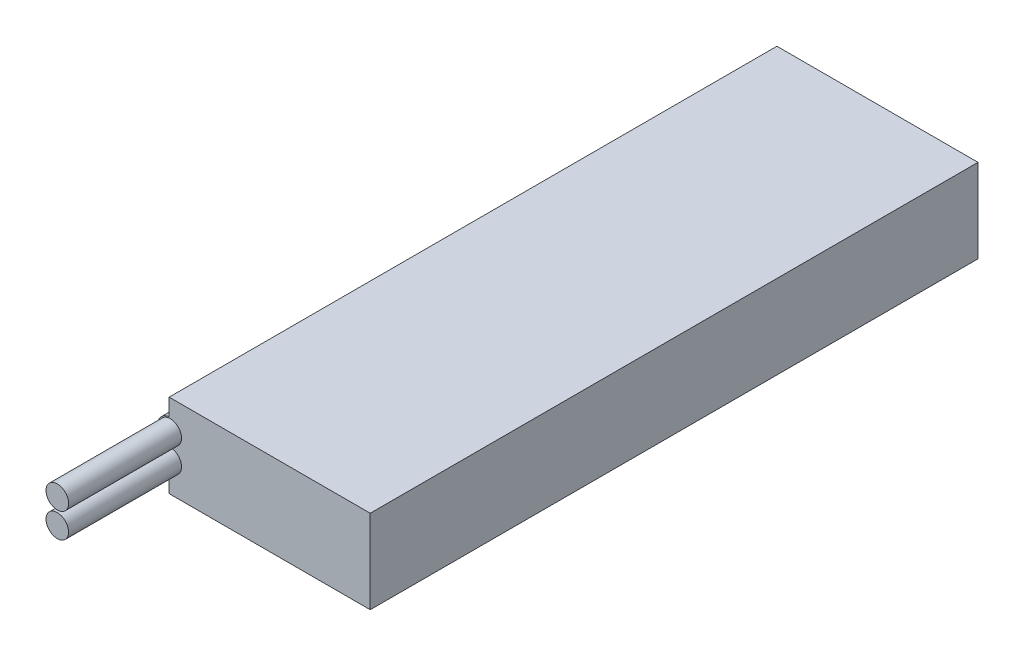
SolidWorks part; units mm, degrees
material "PLA_Battery"
ref_plane "Front Plane" through (0, 0, 0) normal (0, 0, 1) x (1, 0, 0)
ref_plane "Top Plane" through (0, 0, 0) normal (0, 1, 0) x (1, 0, 0)
ref_plane "Right Plane" through (0, 0, 0) normal (1, 0, 0) x (0, 0, -1)
sketch "Sketch1" plane through (0, 0, 0) normal (0, 1, 0) x (1, 0, 0)
  line L1 (-22.25, -67.25) -> (22.25, -67.25)
  line L2 (-22.25, -67.25) -> (-22.25, 67.25)
  line L3 (-22.25, 67.25) -> (22.25, 67.25)
  line L4 (22.25, -67.25) -> (22.25, 67.25)
  line L5 (-22.25, -67.25) -> (22.25, 67.25) construction
  line L6 (-22.25, 67.25) -> (22.25, -67.25) construction
  point P0 (0, 0)
  dimension "D1" = 44.5
  dimension "D2" = 134.5
extrude "Boss-Extrude1" add sketch "Sketch1" along normal blind 18.5
sketch "Imagen" plane through (0, 18.5, 0) normal (0, 1, 0) x (1, 0, 0)
  line L0 (105.6667, 103.5) -> (539.1806, 103.5) construction
  line L1 (19, -59) -> (19, 75.5) construction
sketch "Sketch3" plane through (0, 0, 67.25) normal (0, 0, 1) x (1, 0, 0)
  line L0 (-22, 12) -> (-22, 6.5) construction
  line L1 (-24.75, 21.3788) -> (-24.75, -8.8152) construction
  line L3 (22.25, 18.5) -> (22.25, 0) construction
  line L4 (-22, 9.25) -> (22.25, 9.25) construction
  line L5 (-22.25, 14.7386) -> (-22.25, 3.7614)
  line L6 (-22.25, 18.5) -> (-22.25, 0) construction
  line L7 (-24.75, 12) -> (-24.75, 6.5)
  circle A0 centre (-22, 12) radius 2.75 construction
  circle A1 centre (-22, 6.5) radius 2.75 construction
  arc A2 (-22.25, 14.7386) -> (-24.75, 12) centre (-22, 12) ccw
  arc A3 (-22.25, 3.7614) -> (-24.75, 6.5) centre (-22, 6.5) cw
  line M9 (-22.25, 18.5) -> (-22.25, 0)
  dimension "D1" = 5.5
  dimension "D2" = 47
extrude "Boss-Extrude2" add sketch "Sketch3" against normal offset from surface (7 mm away) 127.5 contours A1 M9 | A0 M9 | A0 M9 | A1 M9 region at (-23.4148, 9.25, 67.25) up to face at (0, 9.25, -67.25)
sketch "Sketch5" plane through (0, 0, 67.25) normal (0, 0, 1) x (1, 0, 0)
  arc A2 (-24.75, 6.5) -> (-22.25, 3.7614) centre (-22, 6.5) ccw construction
  arc A3 (-22.25, 14.7386) -> (-24.75, 12) centre (-22, 12) ccw construction
  circle A4 centre (-22, 6.5) radius 2.75 construction
  circle A5 centre (-22, 12) radius 2.75 construction
  circle A6 centre (-22, 12) radius 2.5
  circle A7 centre (-22, 6.5) radius 2.5
  dimension "D1" = 0.25
  dimension "D2" = 0.25
extrude "Boss-Extrude4" add sketch "Sketch5" along normal blind 25
